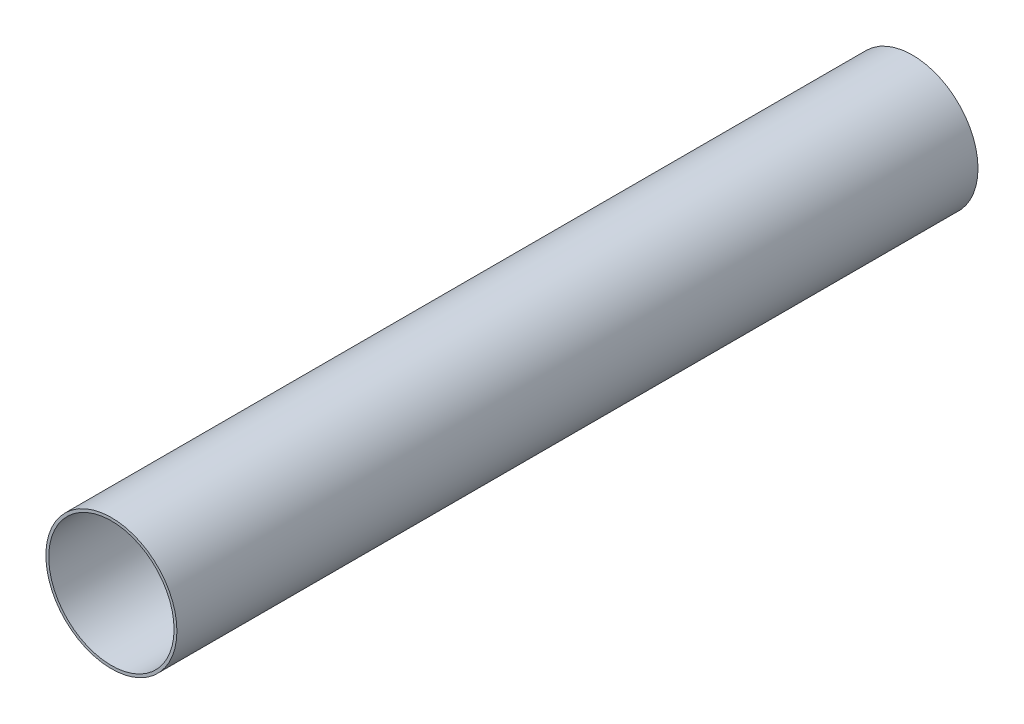
SolidWorks part; units mm, degrees
ref_plane "Front Plane" through (0, 0, 0) normal (0, 0, 1) x (1, 0, 0)
ref_plane "Top Plane" through (0, 0, 0) normal (0, 1, 0) x (1, 0, 0)
ref_plane "Right Plane" through (0, 0, 0) normal (1, 0, 0) x (0, 0, -1)
sketch "Sketch1" plane through (0, 0, 0) normal (0, 0, 1) x (1, 0, 0)
  circle A0 centre (0, 0) radius 28.625
  dimension "D1" = 57.25
extrude "Boss-Extrude3" add sketch "Sketch1" against normal blind 350
sketch "Sketch4" plane through (0, 0, 0) normal (0, 0, 1) x (1, 0, 0)
  circle A0 centre (0, 0) radius 27.375
  dimension "D1" = 54.75
extrude "Cut-Extrude2" cut sketch "Sketch4" against normal up to next
